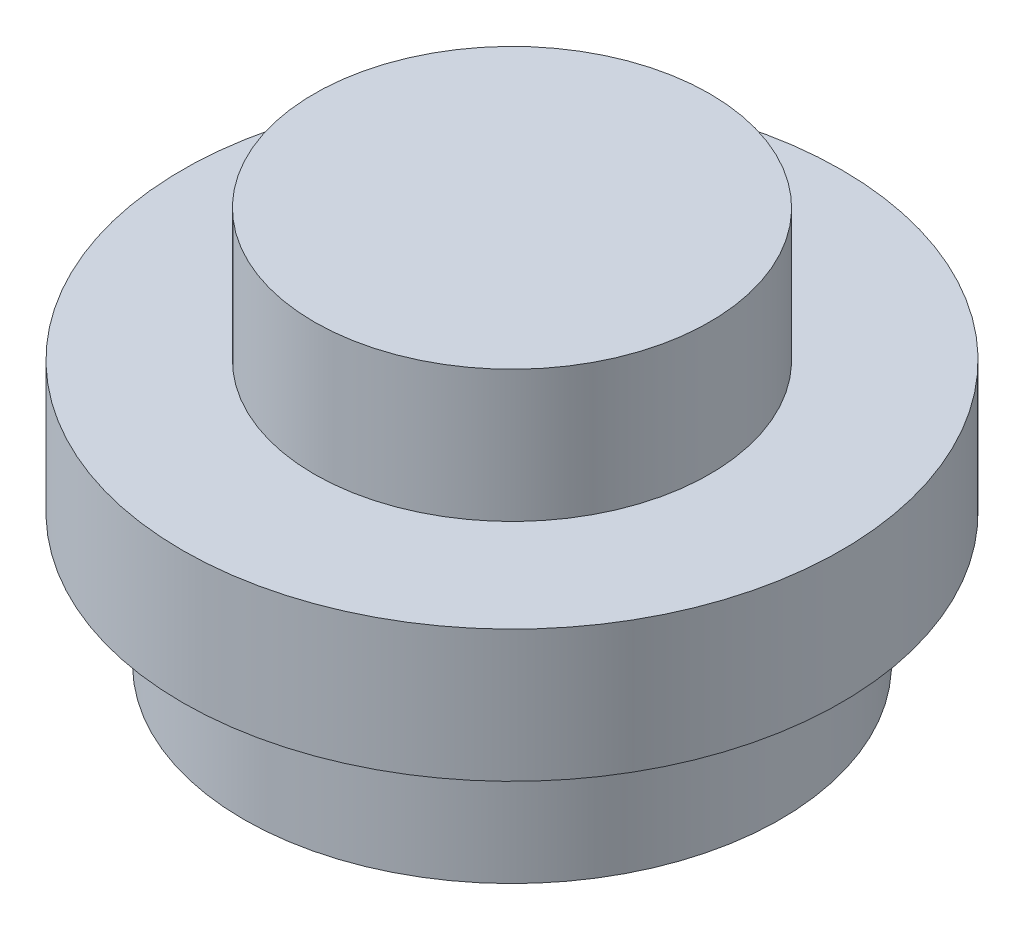
SolidWorks part; units mm, degrees
ref_plane "Front Plane" through (0, 0, 0) normal (0, 0, 1) x (1, 0, 0)
ref_plane "Top Plane" through (0, 0, 0) normal (0, 1, 0) x (1, 0, 0)
ref_plane "Right Plane" through (0, 0, 0) normal (1, 0, 0) x (0, 0, -1)
sketch "Sketch1" plane through (0, 0, 0) normal (0, 1, 0) x (1, 0, 0)
  circle A0 centre (0, 0) radius 2.5
  circle A1 centre (0, 0) radius 2.0355
  circle A2 centre (0, 0) radius 1.5
  dimension "D1" = 5
  dimension "D2" = 3
  dimension "D3" = 4.0711
extrude "Boss-Extrude1" add sketch "Sketch1" along normal blind 2 contours A2 region at (0, 0, 0)
extrude "Boss-Extrude2" add sketch "Sketch1<3>" against normal blind 1 separate body contours A1 A2 region at (-1.978, 0, 0)
sketch "Sketch1<3>" plane through (0, 0, 0) normal (0, 1, 0) x (1, 0, 0) same geometry as "Sketch1"
extrude "Boss-Extrude3" add sketch "Sketch1<4>" along normal blind 1 contours A0
sketch "Sketch1<4>" plane through (0, 0, 0) normal (0, 1, 0) x (1, 0, 0) same geometry as "Sketch1"
sketch "Sketch2" plane through (0, 0, 0) normal (0, -1, 0) x (-1, 0, 0)
  circle A0 centre (0, 0) radius 0.75
  dimension "D1" = 1.5
extrude "Cut-Extrude1" cut sketch "Sketch2" against normal blind 1
